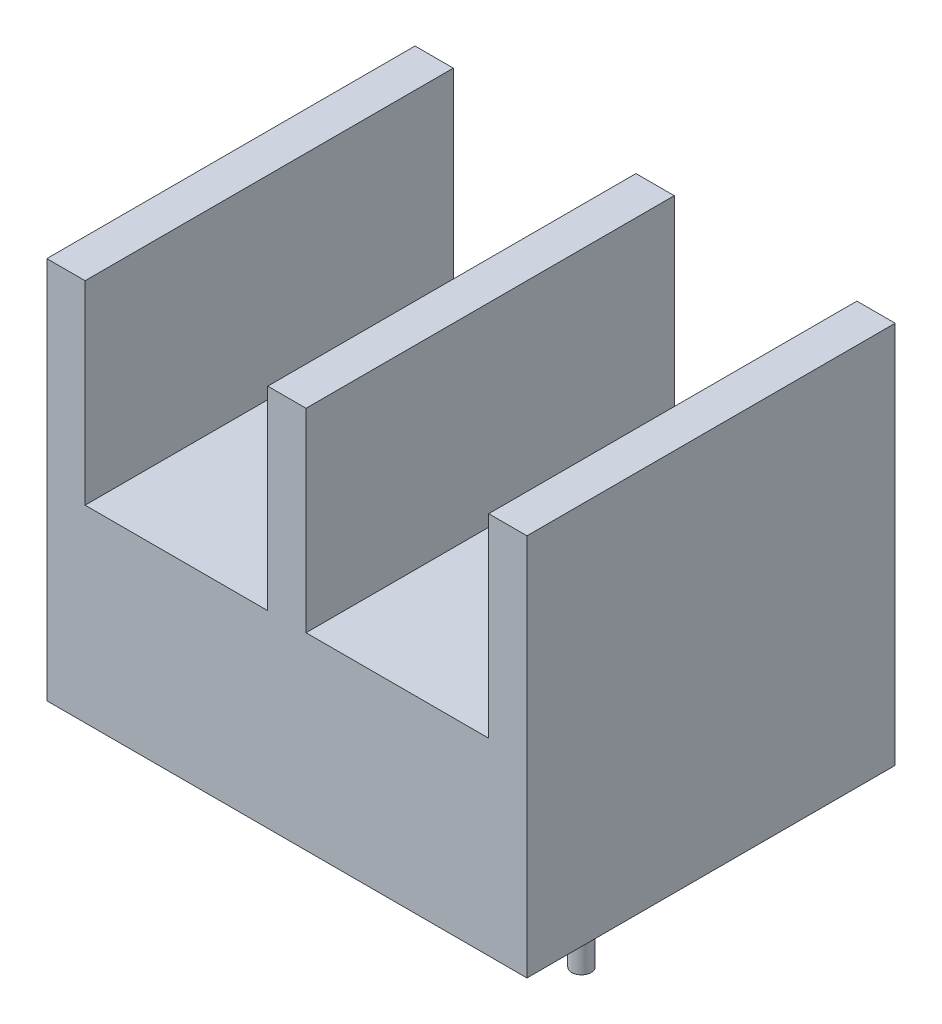
SolidWorks part; units mm, degrees
ref_plane "Front Plane" through (0, 0, 0) normal (0, 0, 1) x (1, 0, 0)
ref_plane "Top Plane" through (0, 0, 0) normal (0, 1, 0) x (1, 0, 0)
ref_plane "Right Plane" through (0, 0, 0) normal (1, 0, 0) x (0, 0, -1)
sketch "Sketch1" plane through (0, 0, 0) normal (0, 1, 0) x (1, 0, 0)
  line L1 (-10.3505, -7.9375) -> (10.3505, -7.9375)
  line L2 (-10.3505, -7.9375) -> (-10.3505, 7.9375)
  line L3 (-10.3505, 7.9375) -> (10.3505, 7.9375)
  line L4 (10.3505, -7.9375) -> (10.3505, 7.9375)
  line L5 (-10.3505, -7.9375) -> (10.3505, 7.9375) construction
  line L6 (-10.3505, 7.9375) -> (10.3505, -7.9375) construction
  point P0 (0, 0)
  dimension "D1" = 15.875
  dimension "D2" = 20.701
extrude "Boss-Extrude1" add sketch "Sketch1" along normal blind 16.51
sketch "Sketch2" plane through (0, 0, 0) normal (0, -1, 0) x (-1, 0, 0)
  line L1 (5.1816, 0.4191) -> (4.3434, 0.4191)
  line L2 (5.1816, 0.4191) -> (5.1816, -0.4191)
  line L3 (5.1816, -0.4191) -> (4.3434, -0.4191)
  line L4 (4.3434, 0.4191) -> (4.3434, -0.4191)
  line L5 (5.1816, 0.4191) -> (4.3434, -0.4191) construction
  line L6 (5.1816, -0.4191) -> (4.3434, 0.4191) construction
  line L7 (-4.3434, 0.4191) -> (-5.1816, 0.4191)
  line L8 (-4.3434, 0.4191) -> (-4.3434, -0.4191)
  line L9 (-4.3434, -0.4191) -> (-5.1816, -0.4191)
  line L10 (-5.1816, 0.4191) -> (-5.1816, -0.4191)
  line L11 (-4.3434, 0.4191) -> (-5.1816, -0.4191) construction
  line L12 (-4.3434, -0.4191) -> (-5.1816, 0.4191) construction
  line L16 (-10.3505, 7.9375) -> (-10.3505, -7.9375)
  line L17 (-10.3505, -7.9375) -> (10.3505, -7.9375)
  line L18 (10.3505, -7.9375) -> (10.3505, 7.9375)
  line L19 (10.3505, 7.9375) -> (-10.3505, 7.9375)
  line L20 (-10.3505, 7.9375) -> (-10.3505, -7.9375)
  line L21 (-10.3505, -7.9375) -> (10.3505, -7.9375)
  line L22 (10.3505, -7.9375) -> (10.3505, 7.9375)
  line L23 (10.3505, 7.9375) -> (-10.3505, 7.9375)
  circle A0 centre (4.7625, 0) radius 0.4191
  circle A1 centre (-4.7625, 0) radius 0.4191
  point P0 (4.7625, 0)
  point P5 (-4.7625, 0)
  point P12 (0, 0)
  dimension "D1" = 9.525
  dimension "D3" = 4.7625
  dimension "D4" = 0.8382
  dimension "D2" = 0
extrude "Boss-Extrude2" add sketch "Sketch2" along normal blind 6.35 contours A1 | A0 region at (-4.7625, 0, 0) region at (4.7625, 0, 0)
ref_point "Point1"
ref_point "Point2"
ref_axis "Axis1" through (-4.7625, -6.35, 0) along (0, -1, 0)
ref_axis "Axis2" through (4.7625, -6.35, 0) along (0, -1, 0)
sketch "Sketch3" plane through (0, 0, -7.9375) normal (0, 0, -1) x (-1, 0, 0)
  line L0 (0, 16.51) -> (0, 0) construction
  line L1 (-10.3505, 16.51) -> (10.3505, 16.51) construction
  line L2 (-10.3505, 0) -> (10.3505, 0) construction
  line L3 (-10.3505, 16.51) -> (-10.3505, 0) construction
  line L4 (-8.6995, 16.51) -> (-0.8255, 16.51)
  line L5 (-8.6995, 16.51) -> (-8.6995, 8.128)
  line L6 (-8.6995, 8.128) -> (-0.8255, 8.128)
  line L7 (-0.8255, 16.51) -> (-0.8255, 8.128)
  line L8 (0.8255, 16.51) -> (8.6995, 16.51)
  line L9 (0.8255, 16.51) -> (0.8255, 8.128)
  line L10 (0.8255, 8.128) -> (8.6995, 8.128)
  line L11 (8.6995, 16.51) -> (8.6995, 8.128)
  line L12 (10.3505, 16.51) -> (10.3505, 0) construction
  line L13 (-0.8255, 8.128) -> (0.8255, 8.128) construction
  line L14 (8.6995, 8.128) -> (10.3505, 8.128) construction
  line L15 (-8.6995, 8.128) -> (-10.3505, 8.128) construction
  point P14 (-4.7625, 8.128)
  point P19 (4.7625, 8.128)
  point P20 (0, 8.128)
  point P21 (0, 0)
  dimension "D1" = 5.588
  dimension "D2" = 5.588
  dimension "D3" = 8.382
extrude "Cut-Extrude1" cut sketch "Sketch3" against normal through all
